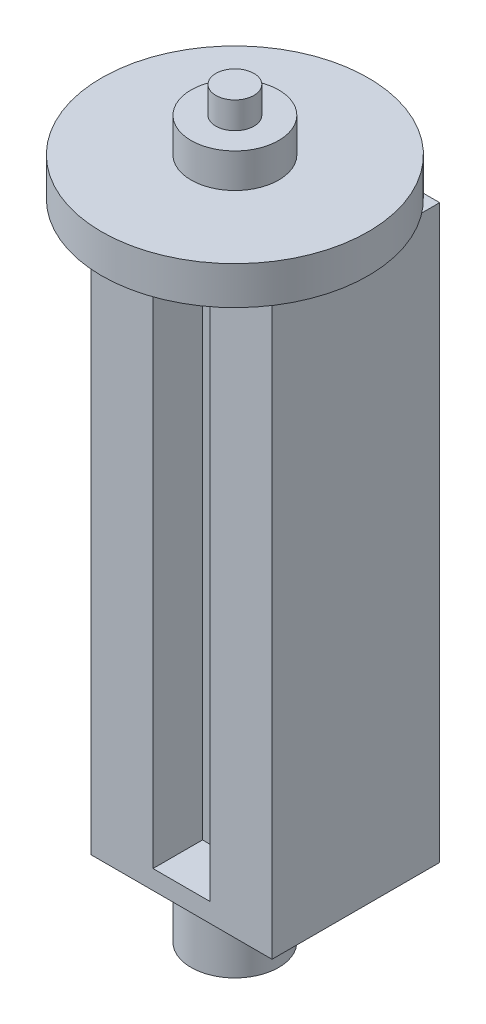
SolidWorks part; units mm, degrees
note: '?' marks a value the reader was unsure of.
ref_plane "Plano frontal" through (0, 0, 0) normal (0, 0, 1) x (1, 0, 0)
ref_plane "Plano superior" through (0, 0, 0) normal (0, 1, 0) x (1, 0, 0)
ref_plane "Plano direito" through (0, 0, 0) normal (1, 0, 0) x (0, 0, -1)
sketch "Esboço1" plane through (0, 0, 0) normal (0, 0, 1) x (1, 0, 0)
  line L1 (-2.375, 7.5) -> (2.375, 7.5)
  line L2 (-2.375, 7.5) -> (-2.375, -7.5)
  line L3 (-2.375, -7.5) -> (2.375, -7.5)
  line L4 (2.375, 7.5) -> (2.375, -7.5)
  line L5 (-2.375, 7.5) -> (2.375, -7.5) construction
  line L6 (-2.375, -7.5) -> (2.375, 7.5) construction
  point P0 (0, 0)
  dimension "D1" = 15
  dimension "D2" = 4.75
extrude "Ressalto-extrusão1" add sketch "Esboço1" along normal blind 4.4 contours L2 L3 L4 L1
sketch "Esboço2" plane through (0, -7.5, 0) normal (0, -1, 0) x (1, 0, 0)
  line L0 (0, 0) -> (0, 3) construction
  line L1 (-2.375, 0) -> (2.375, 0) construction
  circle A0 centre (0, 3) radius 1.15
  dimension "D2" = 2.3
  dimension "D1" = 3
extrude "Ressalto-extrusão2" add sketch "Esboço2" along normal blind 1.5 and the other way offset from surface (18 mm away) 3 other way up to face at (0, 7.5, 2.2)
ref_plane "Plano1" through (0, 8.9, 0) normal (0, 1, 0) x (1, 0, 0)
sketch "Esboço3" plane through (0, 8.9, 0) normal (0, 1, 0) x (1, 0, 0)
  circle A0 centre (0, -3) radius 3.5
  dimension "D1" = 7
extrude "Ressalto-extrusão3" add sketch "Esboço3" against normal blind 1
sketch "Esboço4" plane through (0, 10.5, 0) normal (0, 1, 0) x (1, 0, 0)
  circle A0 centre (0, -3) radius 0.5
  circle A2 centre (0, -3) radius 1.15
  circle A3 centre (0, -3) radius 1.15
  dimension "D1" = 1
  dimension "D2" = 0
extrude "Corte-extrusão1" cut sketch "Esboço4" against normal blind 0.7
sketch "Esboço5" plane through (0, 0, 4.4) normal (0, 0, 1) x (1, 0, 0)
  line L1 (-0.75, 7) -> (0.75, 7)
  line L2 (-0.75, 7) -> (-0.75, -7)
  line L3 (-0.75, -7) -> (0.75, -7)
  line L4 (0.75, 7) -> (0.75, -7)
  line L5 (-0.75, 7) -> (0.75, -7) construction
  line L6 (-0.75, -7) -> (0.75, 7) construction
  point P0 (0, 0)
  dimension "D1" = 1.5
  dimension "D2" = 14
extrude "Corte-extrusão2" cut sketch "Esboço5" against normal blind 1.3
ref_axis "Eixo1" through (0, 11.6738, 3) along (0, -1, 0)?
